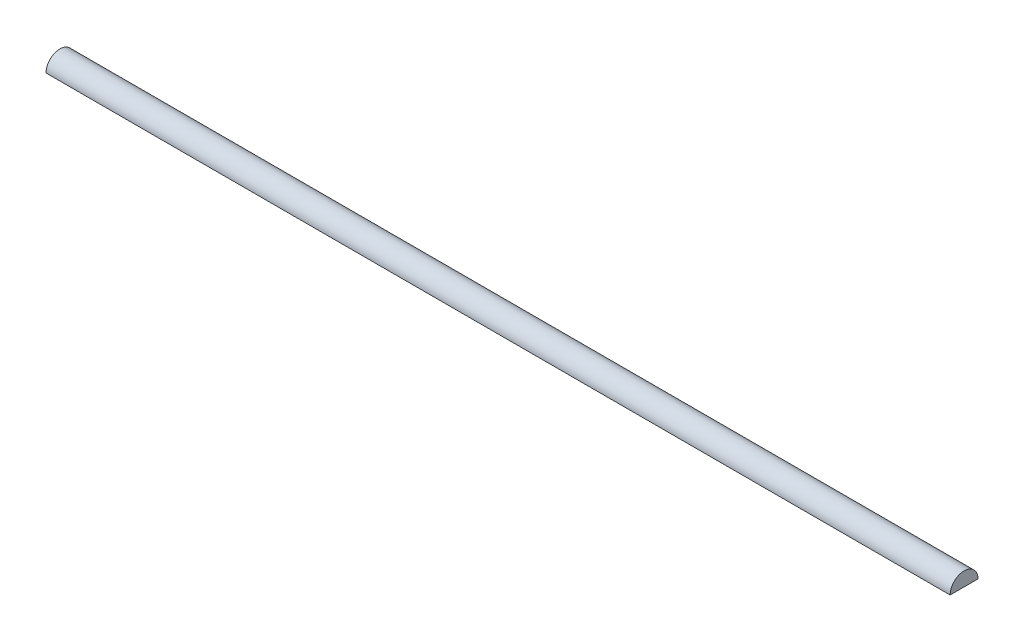
SolidWorks part; units mm, degrees
ref_plane "Front Plane" through (0, 0, 0) normal (0, 0, 1) x (1, 0, 0)
ref_plane "Top Plane" through (0, 0, 0) normal (0, 1, 0) x (1, 0, 0)
ref_plane "Right Plane" through (0, 0, 0) normal (1, 0, 0) x (0, 0, -1)
sketch "Sketch1" plane through (0, 0, 0) normal (0, 1, 0) x (-1, 0, 0)
  line L0 (2034.2432, 337.92) -> (227.583, 983.35)
  line L1 (2034.2432, 337.92) -> (3247.5197, 368.69)
  line L2 (3247.5197, 368.69) -> (3247.5197, 0)
  line L3 (3247.5197, 0) -> (8763.0034, 0)
  line L4 (8763.0034, 0) -> (8763.0034, 1070)
  line L5 (10030.8257, 1120) -> (10227.583, 1070)
  line L6 (10227.583, 1070) -> (8763.0034, 1070)
  line L7 (10030.8257, 1120) -> (5509.8238, 1120)
  line L8 (227.583, 983.35) -> (5509.8238, 1120)
  dimension "D1" = 368.69
  dimension "D2" = 1070
  dimension "D3" = 10000
  dimension "D4" = 50
  dimension "D5" = 337.92
  dimension "D6" = 983.35
revolve "Revolve1" add sketch "Sketch1" angle 360 about L3
sketch "Sketch2" plane through (0, 0, 0) normal (1, 0, 0) x (0, 0, -1)
  circle A0 centre (0, 0) radius 1232.8576
extrude "Boss-Extrude1" add sketch "Sketch2" along normal blind 40000 and the other way blind 40000 separate body
combine bodies "Combine1" operation type subtract main body 102 bodies to subtract 101
sketch "Sketch3" plane through (0, 0, 0) normal (0, 1, 0) x (-1, 0, 0)
  line L0 (40000, -1232.8576) -> (40000, 1232.8576) construction
  line L1 (-40000, 2080.3524) -> (40000, 2080.3524)
  line L2 (-40000, 2080.3524) -> (-40000, -1559.5909)
  line L3 (-40000, -1559.5909) -> (40000, -1559.5909)
  line L4 (40000, 2080.3524) -> (40000, -1559.5909)
  line L5 (-40000, 1232.8576) -> (-40000, -1232.8576) construction
extrude "Cut-Extrude1" cut sketch "Sketch3" against normal through all
